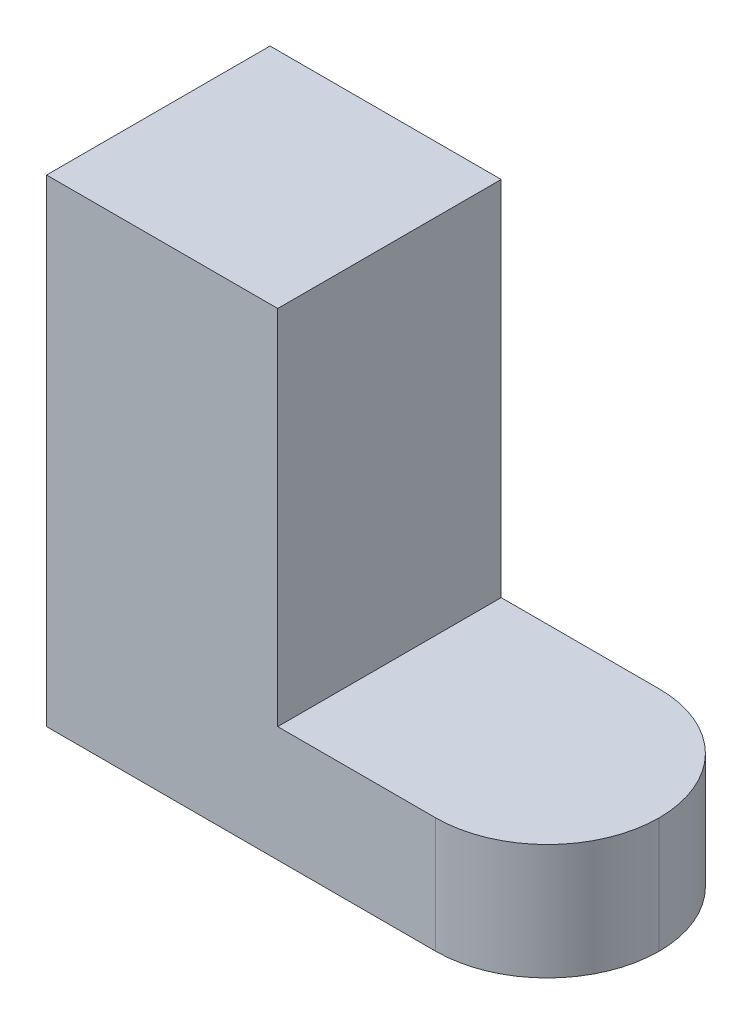
SolidWorks part; units mm, degrees
material "ABS"
ref_plane "Front Plane" through (0, 0, 0) normal (0, 0, 1) x (1, 0, 0)
ref_plane "Top Plane" through (0, 0, 0) normal (0, 1, 0) x (1, 0, 0)
ref_plane "Right Plane" through (0, 0, 0) normal (1, 0, 0) x (0, 0, -1)
sketch "Sketch1" plane through (0, 0, 0) normal (0, 0, 1) x (1, 0, 0)
  line L0 (0, 0) -> (65, 0)
  line L1 (65, 0) -> (65, 15)
  line L2 (65, 15) -> (30, 15)
  line L3 (30, 15) -> (30, 62)
  line L4 (30, 62) -> (0, 62)
  line L5 (0, 62) -> (0, 0)
  dimension "D1" = 62
  dimension "D2" = 65
  dimension "D3" = 15
  dimension "D4" = 30
extrude "Boss-Extrude1" add sketch "Sketch1" along normal mid plane 29
fillet "Fillet1" radius 14.5 2 edges at (65, 7.5, 14.5) (65, 7.5, -14.5)
